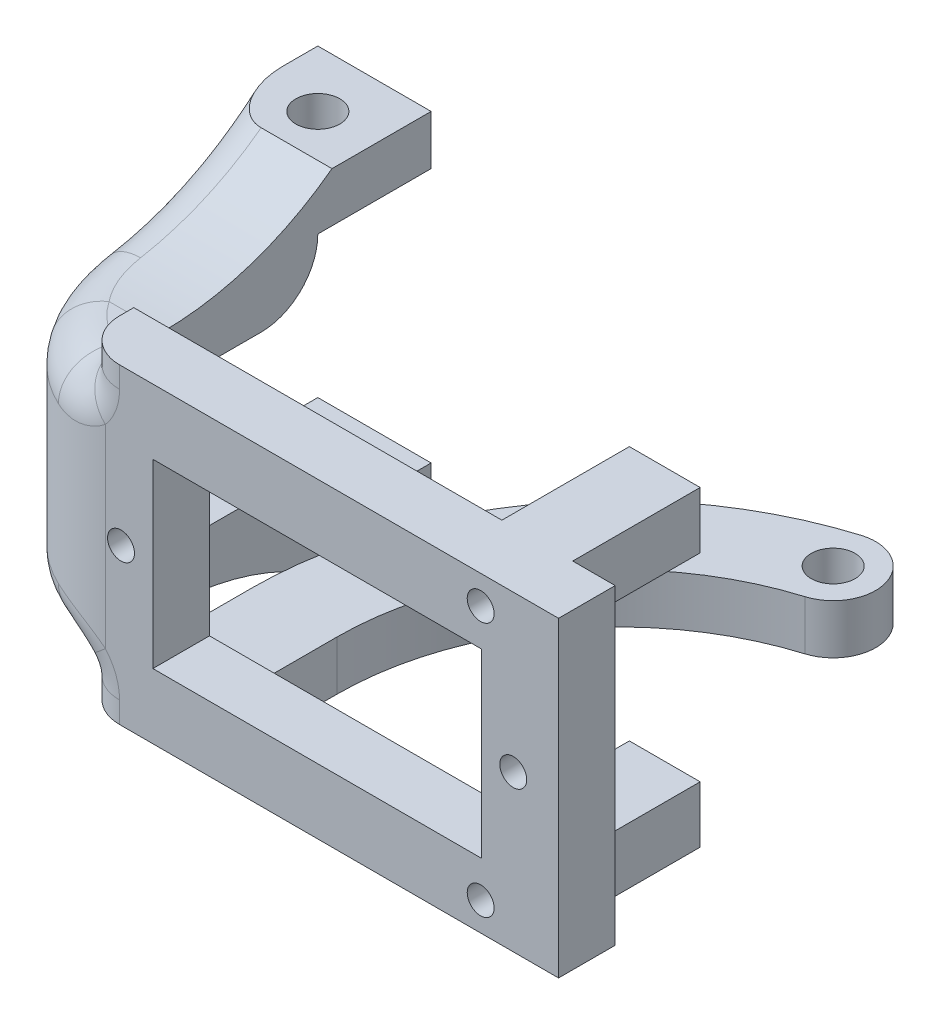
SolidWorks part; units mm, degrees
ref_plane "前视基准面" through (0, 0, 0) normal (0, 0, 1) x (1, 0, 0)
ref_plane "上视基准面" through (0, 0, 0) normal (0, 1, 0) x (1, 0, 0)
ref_plane "右视基准面" through (0, 0, 0) normal (1, 0, 0) x (0, 0, -1)
other "Configuration Table"
sketch "草图1" plane through (0, 0, 0) normal (0, 1, 0) x (1, 0, 0)
  line L0 (0, 0) -> (0, 25)
  line L9 (0, 25) -> (8, 25)
  line L10 (8, 25) -> (8, 4)
  line L11 (8, 4) -> (42, 4)
  line L12 (42, 4) -> (42, 0)
  line L13 (42, 0) -> (0, 0)
  circle A0 centre (4, 21) radius 1.55
  dimension "D5" = 4
  dimension "D6" = 4
  dimension "D7" = 3.1
  dimension "D1" = 42
  dimension "D2" = 8
  dimension "D3" = 4
  dimension "D4" = 25
extrude "凸台-拉伸1" add sketch "草图1" along normal mid plane 25
sketch "草图2" plane through (0, -12.5, 0) normal (0, -1, 0) x (1, 0, 0)
  line L1 (10.8182, -4) -> (16.8182, -4)
  line L4 (10.8182, -9.534) -> (10.8182, -4)
  line L5 (42, -4) -> (8, -4) construction
  line L6 (16.8182, -9.534) -> (16.8182, -4)
  circle A1 centre (30, -31.3923) radius 1.55
  arc A2 (29.1242, -34.2616) -> (30.8758, -28.523) centre (30, -31.3923) ccw
  arc A4 (10.8182, -9.534) -> (29.1242, -34.2616) centre (36.6721, -9.534) ccw
  circle A5 centre (4, -21) radius 1.55 construction
  arc A6 (16.8182, -9.534) -> (30.8758, -28.523) centre (36.6721, -9.534) ccw
  dimension "D1" = 6
  dimension "D2" = 3.1
  dimension "D3" = 6
  dimension "D4" = 28
  dimension "D5" = 26
extrude "凸台-拉伸2" add sketch "草图2" against normal blind 5
sketch "草图3" plane through (0, 0, -4) normal (0, 0, -1) x (-1, 0, 0)
  line L1 (-39, -11) -> (-34, -11)
  line L2 (-39, -11) -> (-39, -7)
  line L3 (-39, -7) -> (-34, -7)
  line L4 (-34, -11) -> (-34, -7)
  line L5 (-42, 12.5) -> (-42, -12.5) construction
  line L6 (-42, -12.5) -> (-16.8182, -12.5) construction
  dimension "D1" = 3
  dimension "D2" = 4
  dimension "D3" = 5
  dimension "D4" = 1.5
extrude "凸台-拉伸3" add sketch "草图3" along normal blind 9
sketch "草图4" plane through (0, 0, -13) normal (0, 0, -1) x (-1, 0, 0)
  line L0 (-39, -7) -> (-39, -11) construction
  line L1 (-34, -7) -> (-39, -7) construction
  circle A0 centre (-36.5, -9) radius 0.95
  dimension "D1" = 2.5
  dimension "D2" = 2
  dimension "D3" = 1.9
extrude "切除-拉伸1" cut sketch "草图4" against normal blind 20
mirror "镜向1" about plane through (0, 0, 0) normal (0, 1, 0) of "凸台-拉伸3", "切除-拉伸1"
sketch "草图5" plane through (0, 0, -4) normal (0, 0, -1) x (-1, 0, 0)
  line L4 (-36.35, 5.7) -> (-36.35, -5.7) construction
  line L5 (-35.85, -6.2) -> (-14.05, -6.2) construction
  line L6 (-13.55, -5.7) -> (-13.55, 5.7) construction
  line L7 (-14.05, 6.2) -> (-35.85, 6.2) construction
  line L8 (-36.55, 6.4) -> (-13.35, 6.4)
  line L9 (-36.35, -6.2) -> (-13.55, -6.2) construction
  line L10 (-36.35, -6.2) -> (-36.35, 6.2) construction
  line L11 (-36.35, 6.2) -> (-13.55, 6.2) construction
  line L12 (-13.55, -6.2) -> (-13.55, 6.2) construction
  line L13 (-36.35, -6.2) -> (-13.55, 6.2) construction
  line L14 (-36.35, 6.2) -> (-13.55, -6.2) construction
  line L15 (-13.35, -6.4) -> (-13.35, 6.4)
  line L16 (-36.55, -6.4) -> (-13.35, -6.4)
  line L17 (-36.55, -6.4) -> (-36.55, 6.4)
  line L18 (-42, 12.5) -> (-42, -12.5) construction
  line L19 (-42, 12.5) -> (-8, 12.5) construction
  point P8 (-24.95, 0)
  dimension "D1" = 0.2
  dimension "D2" = 5.45
  dimension "D3" = 6.1
  dimension "D4" = 12.8
  dimension "D5" = 23.2
extrude "切除-拉伸3" cut sketch "草图5" against normal blind 10 contours L17 L8 L15 L16
sketch "草图6" plane through (0, 0, -4) normal (0, 0, -1) x (-1, 0, 0)
  line L0 (-42, -12.5) -> (-16.8182, -12.5) construction
  line L1 (-42, 12.5) -> (-42, -12.5) construction
  line L2 (-10.8182, -12.5) -> (-8, -12.5) construction
  line L3 (0, 12.5) -> (0, -12.5) construction
  circle A0 centre (-11.1, 0) radius 0.95
  circle A1 centre (-38.8, 0) radius 0.95
  dimension "D1" = 1.9
  dimension "D2" = 1.9
  dimension "D3" = 12.5
  dimension "D4" = 3.2
  dimension "D5" = 12.5
  dimension "D6" = 11.1
extrude "切除-拉伸4" cut sketch "草图6" against normal through all
sketch "草图7" plane through (0, 0, -4) normal (0, 0, -1) x (-1, 0, 0)
  line L0 (-8, 12.5) -> (-8, -12.5) construction
  line L1 (-42, -12.5) -> (-8, -12.5)
  line L2 (-42, -12.5) -> (-42, -11)
  line L3 (-42, -11) -> (-8, -11)
  line L4 (-8, -12.5) -> (-8, -11)
  dimension "D1" = 1.5
extrude "切除-拉伸5" cut sketch "草图7" against normal through all and the other way through all
mirror "镜向2" about plane through (0, 0, 0) normal (0, 1, 0) of "切除-拉伸5"
sketch "草图8" plane through (0, 0, 0) normal (-1, 0, 0) x (0, 0, 1)
  line L1 (0, -12.5) -> (-18, -12.5)
  line L2 (0, -12.5) -> (0, -8.5)
  line L3 (0, -8.5) -> (-18, -8.5)
  line L4 (-18, -12.5) -> (-18, -8.5)
  dimension "D1" = 4
  dimension "D2" = 18
extrude "切除-拉伸6" cut sketch "草图8" against normal blind 8
mirror "镜向3" about plane through (0, 0, 0) normal (0, 1, 0) of "切除-拉伸6"
sketch "草图9" plane through (0, 0, 0) normal (-1, 0, 0) x (0, 0, 1)
  line L0 (-25, 12.5) -> (-25, -12.5) construction
  line L1 (-25, 5) -> (-7, 5)
  line L2 (-25, 5) -> (-25, -5)
  line L3 (-25, -5) -> (-7, -5)
  line L4 (-7, 5) -> (-7, -5)
  point P8 (-7, 0)
  dimension "D1" = 18
  dimension "D2" = 10
extrude "切除-拉伸7" cut sketch "草图9" against normal blind 8
fillet "圆角1" radius 20 2 edges at (4, 8.5, -18) (4, -8.5, -18)
sketch "草图10" plane through (0, 0, 0) normal (-1, 0, 0) x (0, 0, 1)
  line L1 (-25, -5) -> (-17, -5)
  line L2 (-25, -5) -> (-25, -9)
  line L3 (-25, -9) -> (-17, -9)
  line L4 (-17, -5) -> (-17, -9)
  dimension "D1" = 8
  dimension "D2" = 4
extrude "切除-拉伸8" cut sketch "草图10" against normal blind 8
mirror "镜向4" about plane through (0, 0, 0) normal (0, 1, 0) of "切除-拉伸8"
fillet "圆角2" radius 1 1 edges at (8, 0, -4)
fillet "圆角3" radius 1 2 edges at (8, -8.5, -2) (8, 8.5, -2)
fillet "圆角4" radius 4 2 edges at (4, 5, -17) (4, -5, -17)
fillet "圆角5" radius 10 1 edges at (0, 0, 0)
fillet "圆角6" radius 3 10 edges at (0, 10.2581, -14.1996) (8, 10.25, -0.202) (7.6396, 8.7313, -0.2826) (3.3165, 8.5, -2.5615) (8, -10.25, -0.202) (7.7894, -8.8861, -0.2474) (3.3165, -8.5, -2.5615) (0.0561, -8.7177, -8.9427) (0.4585, 8.5254, -7.0067) (0, -10.2581, -14.1996)
